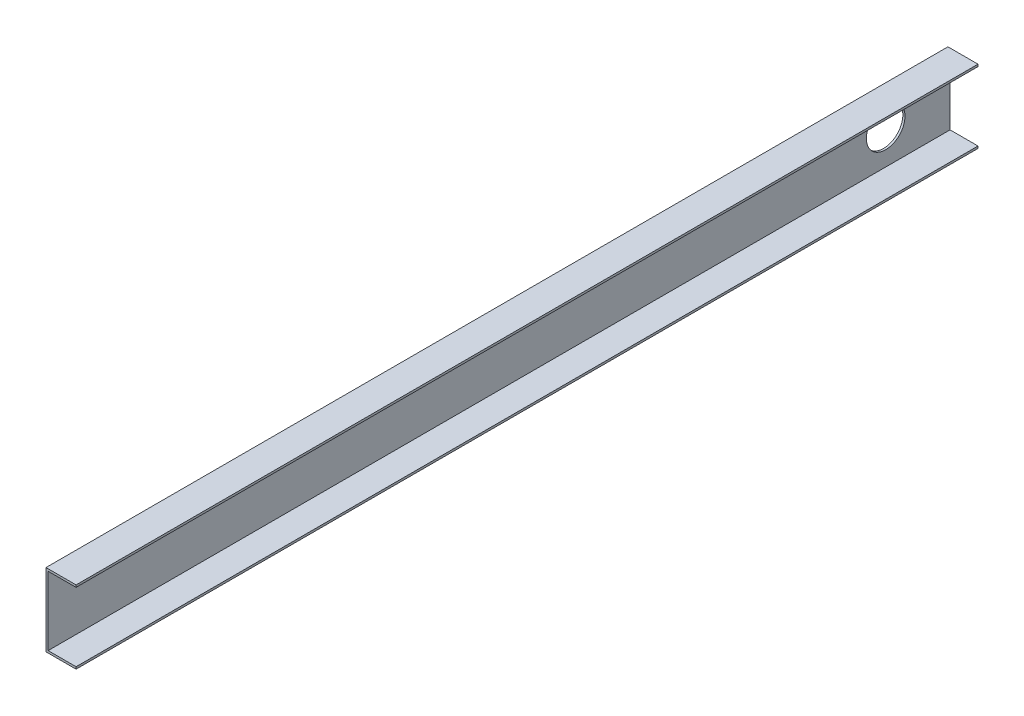
SolidWorks part; units mm, degrees
ref_plane "Plano frontal" through (0, 0, 0) normal (0, 0, 1) x (1, 0, 0)
ref_plane "Plano superior" through (0, 0, 0) normal (0, 1, 0) x (1, 0, 0)
ref_plane "Plano direito" through (0, 0, 0) normal (1, 0, 0) x (0, 0, -1)
sketch "Esboço1" plane through (0, 0, 0) normal (0, 0, 1) x (1, 0, 0)
  line L0 (0, -8.5) -> (0, 8.5)
  line L1 (0, 8.5) -> (7, 8.5)
  line L2 (0, -8.5) -> (7, -8.5)
  line L3 (0.5, -8) -> (7, -8)
  line L4 (0.5, -8) -> (0.5, 8)
  line L5 (0.5, 8) -> (7, 8)
  line L6 (7, -8.5) -> (7, -8)
  line L7 (7, 8.5) -> (7, 8)
  point P4 (0, 0)
  dimension "D1" = 17
  dimension "D2" = 7
  dimension "D3" = 0.5
extrude "Ressalto-extrusão1" add sketch "Esboço1" along normal blind 210
sketch "Esboço3" plane through (0, 0, 0) normal (-1, 0, 0) x (0, 0, 1)
  circle A0 centre (15, 0) radius 4.5
  point P2 (0, 0)
  dimension "D1" = 9
  dimension "D2" = 15
extrude "Corte-extrusão1" cut sketch "Esboço3" against normal blind 10
